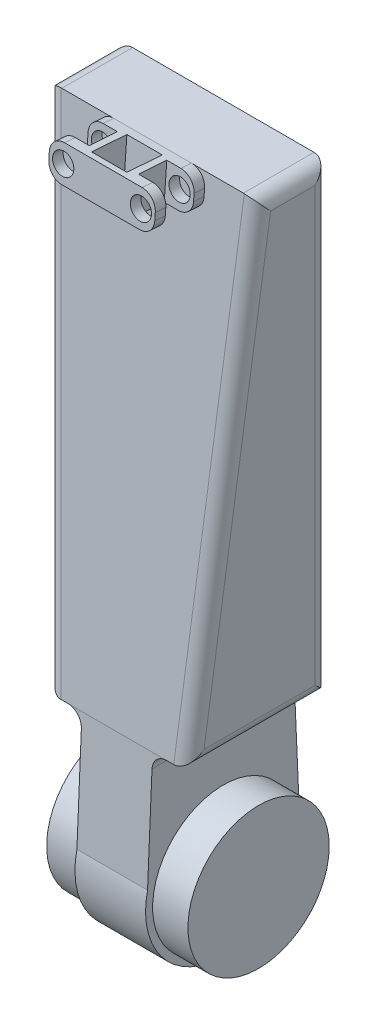
SolidWorks part; units mm, degrees
ref_plane "Alzado" through (0, 0, 0) normal (0, 0, 1) x (1, 0, 0)
ref_plane "Planta" through (0, 0, 0) normal (0, 1, 0) x (1, 0, 0)
ref_plane "Vista lateral" through (0, 0, 0) normal (1, 0, 0) x (0, 0, -1)
sketch "Croquis1" plane through (0, 0, 0) normal (0, 1, 0) x (1, 0, 0)
  line L1 (10, -10) -> (-10, -10)
  line L2 (10, -10) -> (10, 10)
  line L3 (10, 10) -> (-10, 10)
  line L4 (-10, -10) -> (-10, 10)
  line L5 (10, -10) -> (-10, 10) construction
  line L6 (10, 10) -> (-10, -10) construction
  point P0 (0, 0)
  dimension "D1" = 20
  dimension "D2" = 20
ref_plane "Plano1" through (0, 70, 0) normal (0, 1, 0) x (1, 0, 0)
sketch "Croquis2" plane through (0, 70, 0) normal (0, 1, 0) x (1, 0, 0)
  line L1 (15, -5) -> (-15, -5)
  line L2 (15, -5) -> (15, 5)
  line L3 (15, 5) -> (-15, 5)
  line L4 (-15, -5) -> (-15, 5)
  line L5 (15, -5) -> (-15, 5) construction
  line L6 (15, 5) -> (-15, -5) construction
  point P0 (0, 0)
  dimension "D1" = 30
  dimension "D2" = 10
loft "Recubrir1" add profiles "Croquis2", "Croquis1"
sketch "Croquis4" plane through (0, 0, 0) normal (1, 0, 0) x (0, 0, -1)
  line L1 (-10, 0) -> (-10.7192, -16.5305)
  line L2 (10, 0) -> (10.7192, -16.5305)
  line L3 (-10, 0) -> (10, 0)
  arc A2 (-10.7192, -16.5305) -> (10.7192, -16.5305) centre (0, -19) ccw
  point P3 (0, -30)
  dimension "D2" = 30
  dimension "D1" = 22
extrude "Saliente-Extruir1" add sketch "Croquis4" along normal mid plane 10
sketch "Croquis5" plane through (0, 0, 0) normal (1, 0, 0) x (0, 0, -1)
  circle A0 centre (0, -19) radius 10
  dimension "D1" = 20
extrude "Saliente-Extruir2" add sketch "Croquis5" along normal mid plane 20
sketch "Croquis6" plane through (0, 0.7107, 9.9492) normal (0, 0.0712, 0.9975) x (1, 0, 0)
  line L0 (15, 69.4659) -> (-15, 69.4659) construction
  line L1 (-5.5, 64.4659) -> (5.5, 64.4659)
  line L2 (-7.5, 66.4659) -> (-7.5, 67.4659)
  line L3 (-5.5, 69.4659) -> (5.5, 69.4659)
  line L4 (7.5, 66.4659) -> (7.5, 67.4659)
  line L5 (-7.5, 64.4659) -> (7.5, 69.4659) construction
  line L6 (-7.5, 69.4659) -> (7.5, 64.4659) construction
  arc A0 (-7.5, 67.4659) -> (-5.5, 69.4659) centre (-5.5, 67.4659) cw
  arc A1 (-7.5, 66.4659) -> (-5.5, 64.4659) centre (-5.5, 66.4659) ccw
  arc A2 (7.5, 66.4659) -> (5.5, 64.4659) centre (5.5, 66.4659) cw
  arc A3 (5.5, 69.4659) -> (7.5, 67.4659) centre (5.5, 67.4659) cw
  circle A4 centre (-5.5, 66.9659) radius 1.5
  circle A5 centre (5.5, 66.9659) radius 1.5
  point P0 (0, 66.9659)
  dimension "D3" = 2
  dimension "D4" = 2
  dimension "D5" = 2
  dimension "D6" = 2
  dimension "D7" = 3
  dimension "D8" = 3
  dimension "D1" = 15
  dimension "D2" = 5
extrude "Saliente-Extruir3" add sketch "Croquis6" along normal blind 7
sketch "Croquis7" plane through (0, 69.2893, -4.9492) normal (0, 0.9975, -0.0712) x (1, 0, 0)
  line L0 (-7.5, -13.4746) -> (7.5, -13.4746) construction
  line L1 (-7.5, -16.9746) -> (-7.5, -9.9746) construction
  line L2 (7.5, -16.9746) -> (7.5, -9.9746) construction
  line L3 (-5.5, -16.9746) -> (-5.5, -9.9746) construction
  line L4 (-3.5, -15.4746) -> (-7.5, -15.4746)
  line L5 (-3.5, -15.4746) -> (-3.5, -11.4746)
  line L6 (-3.5, -11.4746) -> (-7.5, -11.4746)
  line L7 (-7.5, -15.4746) -> (-7.5, -11.4746)
  line L8 (-3.5, -15.4746) -> (-7.5, -11.4746) construction
  line L9 (-3.5, -11.4746) -> (-7.5, -15.4746) construction
  line L10 (5.5, -16.9746) -> (5.5, -9.9746) construction
  line L11 (3.5, -15.4746) -> (7.5, -15.4746)
  line L12 (3.5, -15.4746) -> (3.5, -11.4746)
  line L13 (3.5, -11.4746) -> (7.5, -11.4746)
  line L14 (7.5, -15.4746) -> (7.5, -11.4746)
  line L15 (3.5, -15.4746) -> (7.5, -11.4746) construction
  line L16 (3.5, -11.4746) -> (7.5, -15.4746) construction
  point P6 (-5.5, -13.4746)
  point P13 (5.5, -13.4746)
  dimension "D1" = 4
  dimension "D2" = 4
extrude "Cortar-Extruir1" cut sketch "Croquis7" against normal mid plane 10
fillet "Redondeo1" radius 2 10 edges
sketch "Croquis8" plane through (0, 69.2893, -4.9492) normal (0, 0.9975, -0.0712) x (1, 0, 0)
  line L0 (5.5, -9.9746) -> (-5.5, -9.9746) construction
  line L1 (-2.5, -16.1215) -> (2.5, -16.1215)
  line L2 (-2.5, -16.1215) -> (-2.5, -11.1215)
  line L3 (-2.5, -11.1215) -> (2.5, -11.1215)
  line L4 (2.5, -16.1215) -> (2.5, -11.1215)
  line L5 (-2.5, -16.1215) -> (2.5, -11.1215) construction
  line L6 (-2.5, -11.1215) -> (2.5, -16.1215) construction
  point P0 (0, -13.6215)
  point P6 (0, 0)
  point P9 (0, -9.9746)
  dimension "D1" = 5
  dimension "D2" = 5
extrude "Cortar-Extruir2" cut sketch "Croquis8" against normal blind 10
